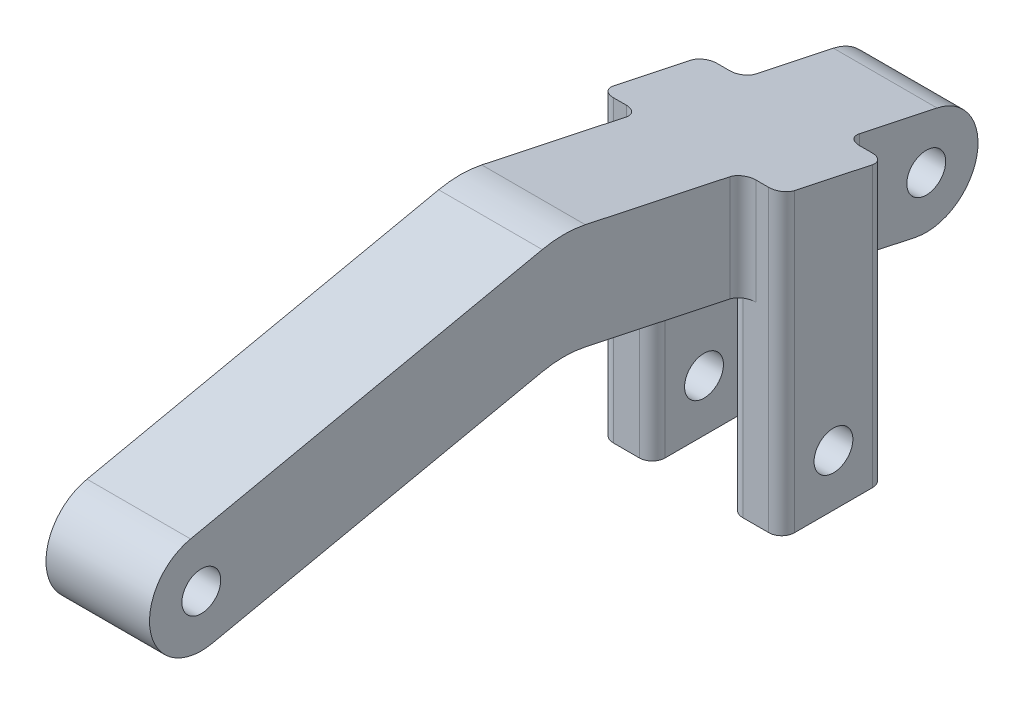
SolidWorks part; units mm, degrees
ref_plane "Alzado" through (0, 0, 0) normal (0, 0, 1) x (1, 0, 0)
ref_plane "Planta" through (0, 0, 0) normal (0, 1, 0) x (1, 0, 0)
ref_plane "Vista lateral" through (0, 0, 0) normal (1, 0, 0) x (0, 0, -1)
sketch "Croquis1" plane through (0, 0, 0) normal (1, 0, 0) x (0, 0, -1)
  line L0 (-28.8316, 3.9126) -> (0, 10.0409) construction
  line L9 (0, 10.0409) -> (28.8316, 3.9126) construction
  line L10 (-27.1684, -3.9126) -> (0, 1.8622) construction
  line L15 (-28, 0) -> (28, 0) construction
  line L16 (0, 1.8622) -> (27.1684, -3.9126) construction
  line L17 (-28.8316, 3.9126) -> (-1.6633, 9.6874)
  line L18 (1.6633, 9.6874) -> (28.8316, 3.9126)
  line L19 (-27.1684, -3.9126) -> (-1.6633, 1.5087)
  line L20 (1.6633, 1.5087) -> (27.1684, -3.9126)
  circle A2 centre (-28, 0) radius 1.5
  circle A4 centre (28, 0) radius 1.5
  arc A7 (-28.8316, 3.9126) -> (-27.1684, -3.9126) centre (-28, 0) ccw
  arc A8 (27.1684, -3.9126) -> (28.8316, 3.9126) centre (28, 0) ccw
  arc A9 (-1.6633, 9.6874) -> (1.6633, 9.6874) centre (0, 1.8622) cw
  arc A10 (-1.6633, 1.5087) -> (1.6633, 1.5087) centre (0, -6.3165) cw
  point P0 (0, 0)
  point P1 (0, 0)
  point P2 (0, 0)
  dimension "D4" = 3
  dimension "D2" = 8
  dimension "D5" = 8
  dimension "D1" = 28
  dimension "D3" = 12
  dimension "D7" = 12
extrude "Saliente-Extruir1" add sketch "Croquis1" along normal mid plane 8
sketch "Croquis3" plane through (0, 0, 0) normal (0, 1, 0) x (1, 0, 0)
  line L1 (4, 28.8316) -> (-4, 28.8316) construction
  line L2 (-4, 21.8316) -> (-7, 21.8316)
  line L3 (-4, 21.8316) -> (-4, 13.8316)
  line L4 (-4, 13.8316) -> (-7, 13.8316)
  line L5 (-7, 21.8316) -> (-7, 13.8316)
  line L10 (0, 0) -> (0, 28.8316) construction
  line L13 (4, 13.8316) -> (7, 13.8316)
  line L14 (7, 21.8316) -> (7, 13.8316)
  line L15 (4, 21.8316) -> (7, 21.8316)
  line L16 (4, 21.8316) -> (4, 13.8316)
  line L17 (-4, 28.8316) -> (-4, 1.6633) construction
  point P10 (-7, 17.8316)
  point P11 (-4, 17.8316)
  dimension "D1" = 3
  dimension "D2" = 8
  dimension "D3" = 7
extrude "Saliente-Extruir2" add sketch "Croquis3" against normal up to surface and the other way up to surface up to face at (0, -1.202, -14.4158) other way up to face at (0, 6.8, -15.2475)
sketch "Croquis4" plane through (0, 0, 0) normal (0, -1, 0) x (1, 0, 0)
  line L25 (-7, -13.8316) -> (7, -13.8316)
  line L26 (-7, -13.8316) -> (-7, -21.8316)
  line L27 (-7, -21.8316) -> (7, -21.8316)
  line L28 (7, -13.8316) -> (7, -21.8316)
extrude "Saliente-Extruir3" add sketch "Croquis4" along normal blind 16
sketch "Croquis7" plane through (0, -16, 0) normal (0, -1, 0) x (1, 0, 0)
  line L1 (3, -21.8316) -> (-3, -21.8316)
  line L2 (3, -21.8316) -> (3, -13.8316)
  line L3 (3, -13.8316) -> (-3, -13.8316)
  line L4 (-3, -21.8316) -> (-3, -13.8316)
  line L5 (3, -21.8316) -> (-3, -13.8316) construction
  line L6 (3, -13.8316) -> (-3, -21.8316) construction
  line L8 (4, -13.8316) -> (-4, -13.8316) construction
  line L9 (-7, -21.8316) -> (7, -21.8316) construction
  point P0 (0, -17.8316)
  dimension "D1" = 6
extrude "Cortar-Extruir2" cut sketch "Croquis7" against normal up to surface (13.2218 mm away) up to face at (0, 0.2154, -7.7475)
fillet "Redondeo1" radius 1 12 edges at (4, 3.0116, -13.8316) (4, 1.3111, -21.8316) (-4, 3.0116, -13.8316) (-4, 1.3111, -21.8316) (3, -9.3891, -21.8316) (-3, -9.3891, -21.8316) (-3, -8.5389, -13.8316) (3, -8.5389, -13.8316) (7, -4.4495, -13.8316) (7, -5.2998, -21.8316) (-7, -5.2998, -21.8316) (-7, -4.4495, -13.8316)
sketch "Croquis6" plane through (0, 0, 0) normal (1, 0, 0) x (0, 0, -1)
  line L1 (20.8316, -16) -> (14.8316, -16) construction
  circle A0 centre (17.8316, -12) radius 1.5
  point P8 (17.8316, -16)
  dimension "D2" = 3
  dimension "D1" = 12
extrude "Cortar-Extruir1" cut sketch "Croquis6" against normal through all both and the other way through all
